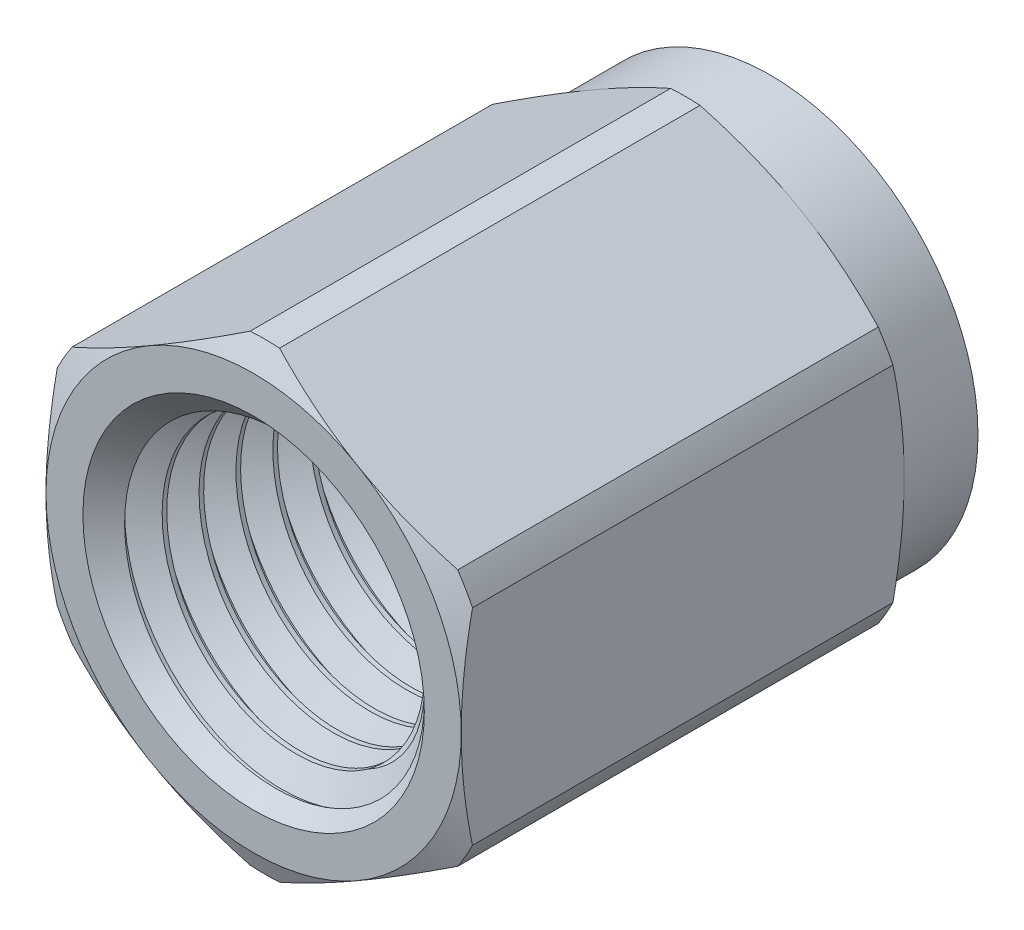
SolidWorks part; units mm, degrees
ref_plane "Front Plane" through (0, 0, 0) normal (0, 0, 1) x (1, 0, 0)
ref_plane "Top Plane" through (0, 0, 0) normal (0, 1, 0) x (1, 0, 0)
ref_plane "Right Plane" through (0, 0, 0) normal (1, 0, 0) x (0, 0, -1)
sketch "Sketch1" plane through (0, 0, 0) normal (1, 0, 0) x (0, 0, -1)
  line L0 (0, -7.1438) -> (0, 7.1438) construction
  line L1 (-8.89, 0) -> (8.89, 0) construction
  line L2 (8.89, 3.302) -> (8.89, -3.302) construction
  line L3 (-8.89, 5.5562) -> (-8.89, -5.5562) construction
  line L4 (-10.0806, 5.6937) -> (-8.8106, 5.6937) construction
  line L5 (-8.8106, 5.6937) -> (-9.4456, 4.5939) construction
  line L6 (-9.4456, 4.5939) -> (-10.0806, 5.6937) construction
  line L7 (-9.4456, 4.5939) -> (-9.4456, 4.7314) construction
  line L8 (-9.525, 4.7314) -> (-9.3662, 4.7314) construction
  line L9 (-9.4456, 5.5562) -> (-9.4456, 5.6937) construction
  line L11 (-8.89, 5.5562) -> (-10.0012, 5.5562) construction
  line L14 (-10.0409, 5.625) -> (-8.8503, 5.625) construction
  point P5 (0, 0)
  point P8 (8.89, 0)
  point P18 (-9.4456, 5.625)
  point P20 (8.89, 3.175)
  point P24 (8.89, -3.175)
  dimension "Hex" = 14.2875
  dimension "Length" = 17.78
  dimension "Hole Diameter" = 6.604
  dimension "Thread Diameter" = 11.1125
  dimension "Pitch" = 1.27
  dimension "D1" = 0.1588
  dimension "Tube OD" = 6.35
sketch "Sketch2" plane through (0, 0, 0) normal (0, 0, 1) x (1, 0, 0)
  line L0 (0, 7.1438) -> (0, 7.42) construction
  line L1 (-0.5064, 7.9565) -> (-6.6373, 4.4168)
  line L2 (-7.1438, 3.5397) -> (-7.1438, -3.5397)
  line L3 (-6.6373, -4.4168) -> (-0.5064, -7.9565)
  line L4 (0.5064, -7.9565) -> (6.6373, -4.4168)
  line L5 (7.1438, -3.5397) -> (7.1438, 3.5397)
  line L6 (6.6373, 4.4168) -> (0.5064, 7.9565)
  line L7 (0, 7.42) -> (0, 7.6963) construction
  line L8 (0, 7.6963) -> (0, 7.9726) construction
  line L9 (0, 7.9726) -> (0, 8.2489) construction
  line L10 (-0.5064, 7.9565) -> (0, 8.2489) construction
  line L11 (0, 8.2489) -> (0.5064, 7.9565) construction
  line L12 (0, 0) -> (3.9289, -3.9289) construction
  circle A0 centre (0, 0) radius 7.1438 construction
  arc A1 (0.5064, 7.9565) -> (-0.5064, 7.9565) centre (0, 0) ccw
  arc A2 (7.1438, 3.5397) -> (6.6373, 4.4168) centre (0, 0) ccw
  arc A3 (6.6373, -4.4168) -> (7.1438, -3.5397) centre (0, 0) ccw
  arc A4 (-0.5064, -7.9565) -> (0.5064, -7.9565) centre (0, 0) ccw
  arc A5 (-7.1438, -3.5397) -> (-6.6373, -4.4168) centre (0, 0) ccw
  arc A6 (-6.6373, 4.4168) -> (-7.1438, 3.5397) centre (0, 0) ccw
  circle A8 centre (0, 0) radius 5.5562 construction
  point P21 (3.9289, -3.9289)
  dimension "D1" = 135
extrude "Boss-Extrude1" add sketch "Sketch2" along normal up to vertex (8.89 mm away) from vertex up to point (0, 0, 8.89) starting at point (0, 0, -8.89)
sketch "Sketch3" plane through (0, 0, 0) normal (1, 0, 0) x (0, 0, -1)
  line L0 (-8.89, 8.2489) -> (-8.89, 7.1438)
  line L1 (-8.89, 7.1438) -> (-8.3747, 8.2489)
  line L2 (-8.3747, 8.2489) -> (-8.89, 8.2489)
  line L3 (5.8347, 8.2489) -> (6.35, 7.1438)
  line L4 (6.35, 7.1438) -> (8.89, 7.1438)
  line L5 (8.89, 7.1438) -> (8.89, 8.2489)
  line L6 (8.89, 8.2489) -> (5.8347, 8.2489)
  line L7 (-8.89, 5.8737) -> (-8.5725, 5.5562)
  line L8 (-8.89, 4.4168) -> (-8.89, 7.9565) construction
  line L9 (-8.5725, 5.5562) -> (6.35, 5.5562)
  line L10 (6.35, 5.5562) -> (6.35, 3.302)
  line L11 (6.35, 3.302) -> (8.89, 3.302)
  line L12 (8.89, 3.302) -> (8.89, 0)
  line L13 (8.89, 3.302) -> (8.89, -3.302) construction
  line L14 (8.89, 0) -> (-8.89, 0)
  line L15 (-8.89, 5.8737) -> (-8.89, 0)
  dimension "D1" = 2.54
  dimension "D2" = 25
  dimension "D3" = 25
  dimension "D4" = 45
  dimension "D5" = 0.3175
revolve "Cut-Revolve1" cut sketch "Sketch3" angle 360 about L14
sketch "Sketch4" plane through (0, 0, 8.89) normal (0, 0, 1) x (1, 0, 0)
  circle A0 centre (0, 0) radius 5.5562
curve "Helix/Spiral1" pitch 1.27 height 21.59 radius 5.5562 centre (0, 0, 8.89) axis (0, 0, -1) start towards (0, 1, 0)
sketch "Sketch5" plane through (0, 0, 0) normal (1, 0, 0) x (0, 0, -1)
  line L0 (-8.8503, 5.625) -> (-9.3662, 4.7314)
  line L1 (-9.3662, 4.7314) -> (-9.525, 4.7314)
  line L2 (-9.525, 4.7314) -> (-10.0409, 5.625)
  line L3 (-10.0409, 5.625) -> (-8.8503, 5.625)
sweep "Sweep1" add profiles "Sketch5" path "Helix/Spiral1"
sketch "Sketch6" plane through (0, 0, 8.89) normal (0, 0, 1) x (1, 0, 0)
  line L0 (0, -5.8737) -> (0, 0) construction
  line L1 (0, 0) -> (4.1534, -4.1534) construction
  circle A0 centre (0, 0) radius 5.8737 construction
  circle A1 centre (0, 0) radius 5.8737
  circle A2 centre (0, 0) radius 3.175 construction
  point P3 (4.1534, -4.1534)
  dimension "D1" = 45
extrude "Cut-Extrude1" cut sketch "Sketch6" against normal through all draft 45 and the other way through all
sketch "Sketch7" plane through (0, 0, -8.89) normal (0, 0, -1) x (-1, 0, 0)
  circle A0 centre (0, 0) radius 3.302 construction
  circle A1 centre (0, 0) radius 3.302
  circle A2 centre (0, 0) radius 7.1438 construction
  circle A3 centre (0, 0) radius 7.1438
extrude "Cut-Extrude2" cut sketch "Sketch7" along normal through all
equation "\"D1@Sketch1\"=\"Pitch@Sketch1\"/8"
equation "\"D5@Sketch3\"=.25*\"Pitch@Sketch1\""
equation "\"D4@Helix/Spiral1\"=\"Pitch@Sketch1\""
equation "\"D3@Helix/Spiral1\"=\"Length@Sketch1\"+3*\"Pitch@Sketch1\""
